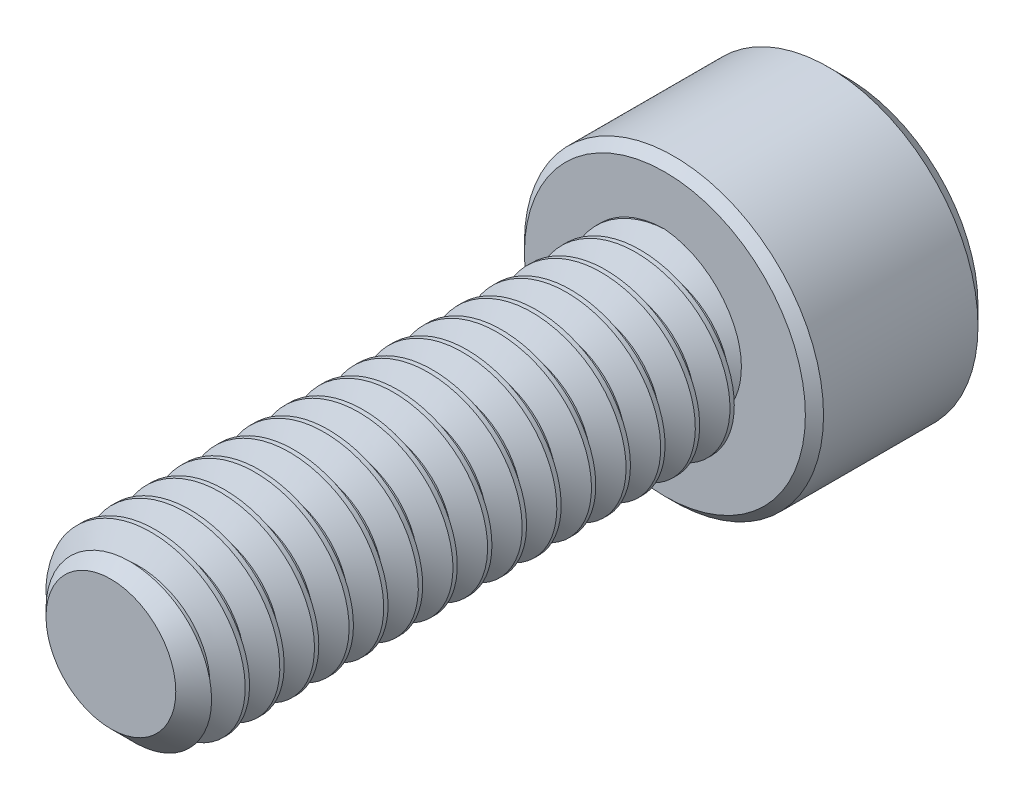
SolidWorks part; units mm, degrees
ref_plane "Front Plane" through (0, 0, 0) normal (0, 0, 1) x (1, 0, 0)
ref_plane "Top Plane" through (0, 0, 0) normal (0, 1, 0) x (1, 0, 0)
ref_plane "Right Plane" through (0, 0, 0) normal (1, 0, 0) x (0, 0, -1)
sketch "Sketch1" plane through (0, 0, 0) normal (0, 0, 1) x (1, 0, 0)
  line L0 (0, 2.0828) -> (0, -2.0828) construction
  circle A0 centre (0, 0) radius 2.0828
  dimension "OD" = 4.1656
extrude "Extrude1" add sketch "Sketch1" against normal blind 12.7
sketch "Sketch2" plane through (0, 0, 0) normal (0, 0, 1) x (1, 0, 0)
  circle A0 centre (0, 0) radius 2.0828 construction
  circle A1 centre (0, 0) radius 2.0828
curve "Helix/Spiral1" pitch 0.7937 height 13.4937 turns 17 parameters "pitch"=0.7937
chamfer "Chamfer3" distance 0.5953 angle 45 1 edges at (2.0828, 0, 0)
sketch "Sketch3" plane through (0, 0, 0) normal (1, 0, 0) x (0, 0, -1)
  line L0 (-0.6945, 2.0828) -> (-0.3969, 1.5672)
  line L1 (-0.3969, 1.5672) -> (-0.2977, 1.5672)
  line L2 (-0.2977, 1.5672) -> (0, 2.0828)
  line L3 (-0.6945, 2.0828) -> (0, 2.0828)
  line L4 (-0.3473, 2.0828) -> (-0.3473, 1.5672) construction
  line L5 (-0.5457, 1.825) -> (-0.1488, 1.825) construction
  line L6 (0, 2.0828) -> (0, -2.0828) construction
  dimension "D1" = 0.0992
  dimension "D2" = 0.3969
  dimension "D3" = 60
sweep "Cut-Sweep1" cut profiles "Sketch3" path "Helix/Spiral1"
sketch "Sketch6" plane through (0, 0, -12.7) normal (0, 0, -1) x (-1, 0, 0)
  circle A0 centre (0, 0) radius 3.429
  dimension "head dia" = 6.858
extrude "Extrude2" add sketch "Sketch6" along normal blind 4.1656
sketch "Sketch7" plane through (0, 0, -16.8656) normal (0, 0, -1) x (-1, 0, 0)
  line L1 (0, 2.0622) -> (-1.7859, 1.0311)
  line L2 (-1.7859, 1.0311) -> (-1.7859, -1.0311)
  line L3 (-1.7859, -1.0311) -> (0, -2.0622)
  line L4 (0, -2.0622) -> (1.7859, -1.0311)
  line L5 (1.7859, -1.0311) -> (1.7859, 1.0311)
  line L6 (1.7859, 1.0311) -> (0, 2.0622)
  circle A0 centre (0, 0) radius 1.7859 construction
  dimension "hex dia" = 3.5719
extrude "Cut-Extrude1" cut sketch "Sketch7" against normal blind 2.6789
sketch "Sketch8" plane through (0, 0, -16.8656) normal (0, 0, -1) x (-1, 0, 0)
  circle A0 centre (0, 0) radius 2.0622
extrude "Cut-Extrude2" cut sketch "Sketch8" against normal blind 0.4166 draft 45
chamfer "Chamfer1" distance 0.4166 angle 45 1 edges at (-3.429, 0, -16.8656)
chamfer "Chamfer2" distance 0.2083 angle 45 1 edges at (-3.429, 0, -12.7)
sketch "Sketch9" plane through (0, 0, 0) normal (1, 0, 0) x (0, 0, -1)
  line L0 (0, 2.0828) -> (0, -2.0828) construction
  line L1 (4.3656, 2.0828) -> (4.3656, -2.0828) construction
  line L2 (12.7, 3.429) -> (12.7, -3.429) construction
  line L3 (16.8656, 3.429) -> (16.8656, -3.429) construction
  line L4 (16.8656, 0) -> (0, 0) construction
  dimension "D1" = 4.3656
  dimension "D2" = 4.1656
  dimension "D3" = 6.858
  dimension "D4" = 12.7
equation "\"D3@Helix/Spiral1\" = \"screw length@Extrude1\"+\"pitch@Helix/Spiral1\""
equation "\"D1@Sketch3\" = \"pitch@Helix/Spiral1\"*.125"
equation "\"D2@Sketch3\" = \"pitch@Helix/Spiral1\"*.5"
equation "\"D1@Cut-Extrude1\" = \"hex dia@Sketch7\"*.75"
equation "\"D1@Chamfer1\" = \"head depth@Extrude2\"/10"
equation "\"D1@Sketch9\" = \"pitch@Helix/Spiral1\"*5.5"
equation "\"D1@Chamfer2\" = \"D1@Chamfer1\"/2"
equation "\"D1@Cut-Extrude2\" = \"D1@Chamfer2\"*2"
equation "\"D1@Chamfer3\" = \"pitch@Helix/Spiral1\"*.750"
equation "\"D2@Sketch9\" = \"head depth@Extrude2\""
equation "\"D3@Sketch9\" = \"head dia@Sketch6\""
equation "\"D4@Sketch9\" = \"screw length@Extrude1\""
